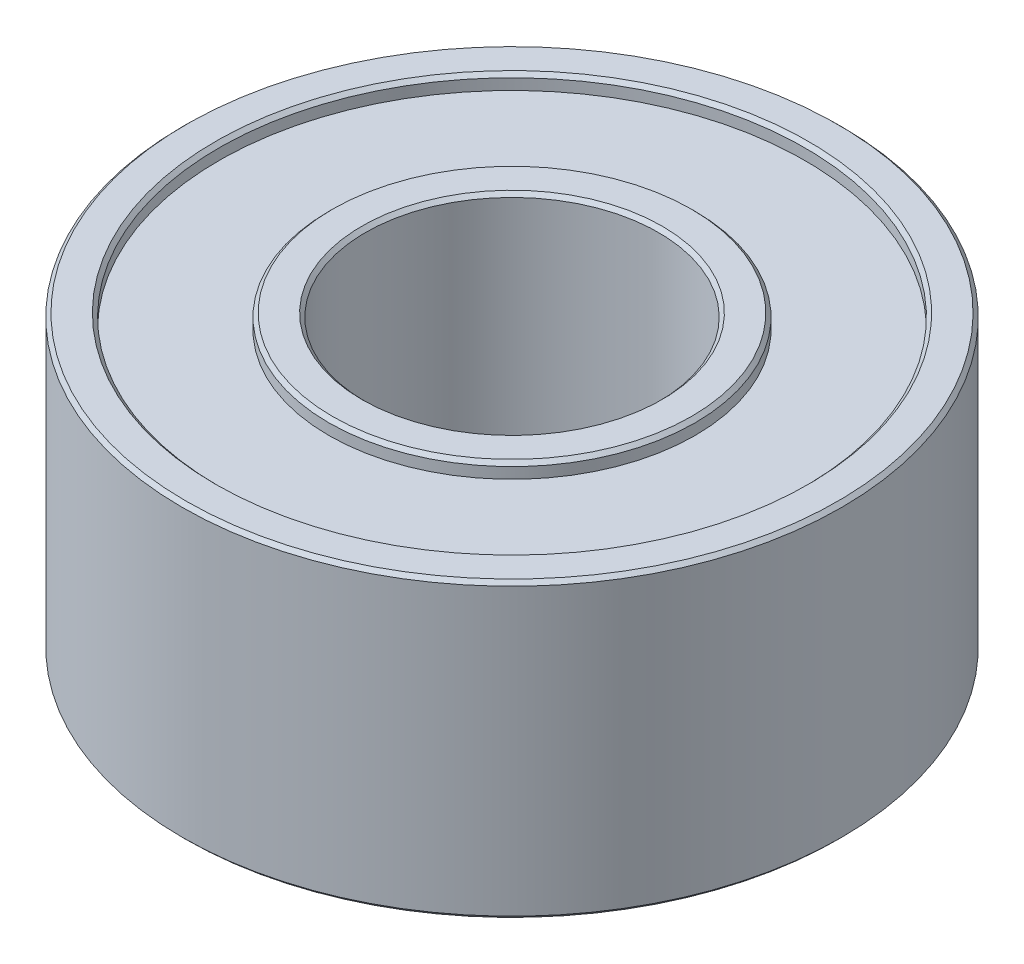
SolidWorks part; units mm, degrees
material "Cast Stainless Steel"
ref_plane "Front Plane" through (0, 0, 0) normal (0, 0, 1) x (1, 0, 0)
ref_plane "Top Plane" through (0, 0, 0) normal (0, 1, 0) x (1, 0, 0)
ref_plane "Right Plane" through (0, 0, 0) normal (1, 0, 0) x (0, 0, -1)
sketch "Sketch1" plane through (0, 0, 0) normal (0, 1, 0) x (1, 0, 0)
  circle A0 centre (0, 0) radius 4.5
  circle A1 centre (0, 0) radius 2
  dimension "D1" = 9
  dimension "D2" = 4
extrude "Boss-Extrude1" add sketch "Sketch1" along normal mid plane 4
sketch "Sketch2" plane through (0, 0, 0) normal (0, 1, 0) x (1, 0, 0)
  circle A0 centre (0, 0) radius 4
  circle A1 centre (0, 0) radius 2.5
  circle A2 centre (0, 0) radius 4.5 construction
  circle A3 centre (0, 0) radius 2 construction
  dimension "D1" = 0.5
  dimension "D2" = 0.5
extrude "Cut-Extrude1" cut sketch "Sketch2" against normal blind 0.2 from surface starting at face at (0, 2, 4.5)
extrude "Cut-Extrude3" cut sketch "Sketch2<2>" along normal blind 0.2 from surface starting at face at (0, -2, 4.5)
sketch "Sketch2<2>" plane through (0, 0, 0) normal (0, 1, 0) x (1, 0, 0) same geometry as "Sketch2"
chamfer "Chamfer1" distance 0.05 angle 45 8 edges at (0, 2, 2.5) (0, -2, 4.5) (0, -2, 4) (0, -2, 2.5) (0, -2, 2) (0, 2, 4.5) (0, 2, 4) (0, 2, 2)
ref_axis "Axis1" through (0, 1.95, 0) along (0, -1, 0)
